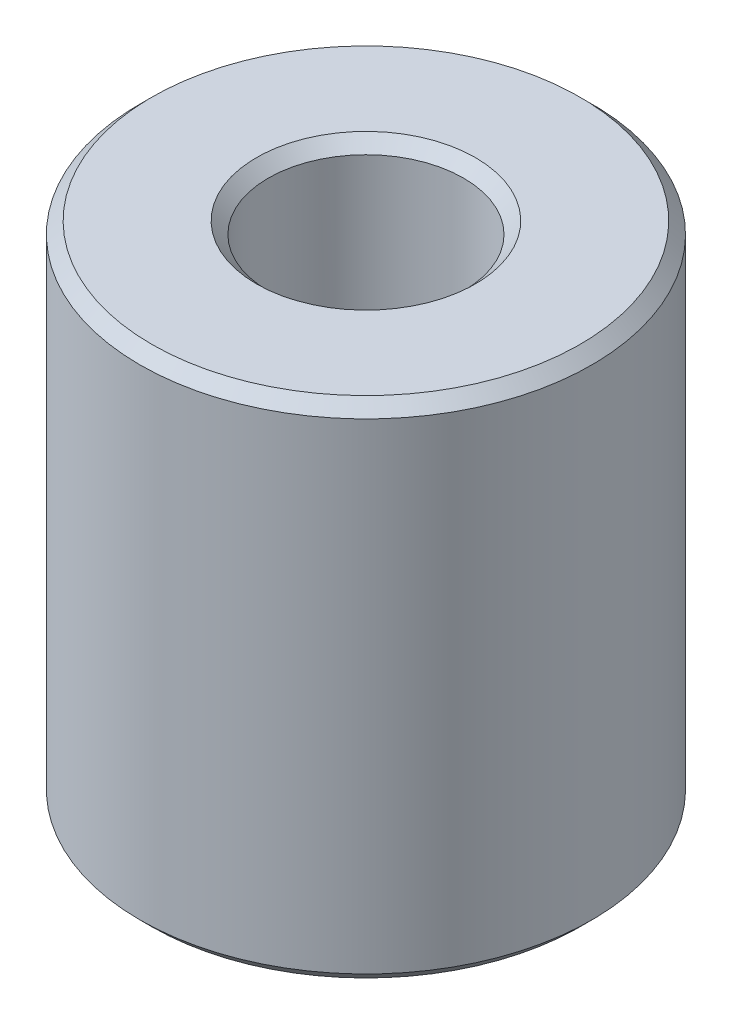
SolidWorks part; units mm, degrees
ref_plane "Front Plane" through (0, 0, 0) normal (0, 0, 1) x (1, 0, 0)
ref_plane "Top Plane" through (0, 0, 0) normal (0, 1, 0) x (1, 0, 0)
ref_plane "Right Plane" through (0, 0, 0) normal (1, 0, 0) x (0, 0, -1)
sketch "Sketch1" plane through (0, 0, 0) normal (0, 1, 0) x (1, 0, 0)
  circle A0 centre (0, 0) radius 15
  dimension "SLEEVE_OD" = 30
extrude "Boss-Extrude1" add sketch "Sketch1" along normal blind 33.48
sketch "Sketch2" plane through (0, 0, 0) normal (0, 1, 0) x (1, 0, 0)
  circle A0 centre (0, 0) radius 6.4816
  dimension "BORE_D" = 12.9632
extrude "Cut-Extrude1" cut sketch "Sketch2" along normal through all
chamfer "Chamfer1" distance 0.7857 angle 45 4 edges at (0, 33.48, 6.4816) (0, 0, 6.4816) (0, 0, 15) (0, 33.48, 15)
